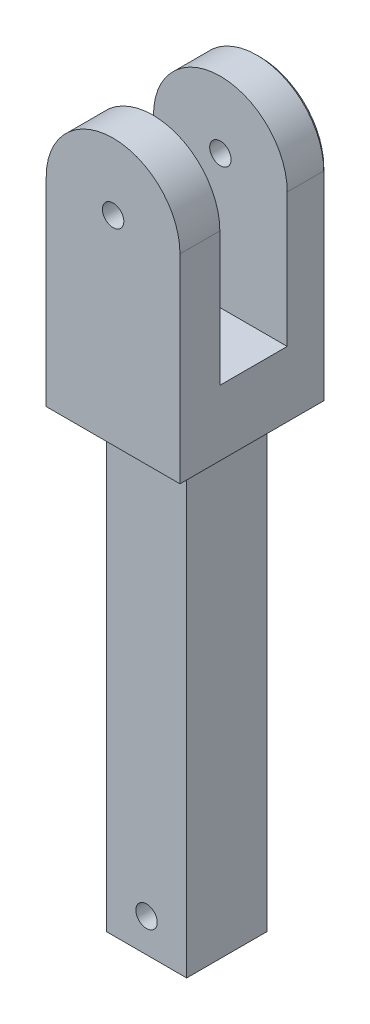
SolidWorks part; units mm, degrees
ref_plane "前基準面" through (0, 0, 0) normal (0, 0, 1) x (1, 0, 0)
ref_plane "上基準面" through (0, 0, 0) normal (0, 1, 0) x (1, 0, 0)
ref_plane "右基準面" through (0, 0, 0) normal (1, 0, 0) x (0, 0, -1)
sketch "草圖1" plane through (0, 0, 0) normal (0, 0, 1) x (1, 0, 0)
  line L0 (0, 0) -> (0, -11.05)
  line L1 (-10, 0) -> (-10, -30.2764)
  line L3 (10, -30.2764) -> (10, 0)
  line L4 (-10, -30.2764) -> (10, -30.2764)
  circle A1 centre (0, 0) radius 1.6
  arc A2 (10, 0) -> (-10, 0) centre (0, 0) ccw
  dimension "D1" = 11.05
  dimension "D2" = 3.2
  dimension "D3" = 20
extrude "填料-伸長1" add sketch "草圖1" along normal blind 12 contours L3 A2 L1 A1 region at (0, -11.2647, 0)
sketch "草圖2" plane through (10, 0, 0) normal (1, 0, 0) x (0, 0, -1)
  line L0 (-12, 0) -> (-9.1, 0)
  line L1 (-12, 0) -> (0, 0) construction
  line L2 (-12, 10) -> (-12, 0) construction
  line L3 (0, 0) -> (-2.9, 0)
  line L4 (-6, 0) -> (-3, 0)
  line L5 (-6, 0) -> (-9, 0)
  line L6 (-9, 0) -> (-9, 15.7808)
  line L7 (-9, 15.7808) -> (-3, 15.7808)
  line L8 (-3, 15.7808) -> (-3, 0)
  line L9 (-3, 0) -> (-3, -20)
  line L10 (-9, 0) -> (-8.6005, -20)
  line L11 (-8.6005, -20) -> (-3, -20)
  line M8 (0, 0) -> (-12, 0)
  dimension "D1" = 2.9
  dimension "D2" = 2.9
  dimension "D3" = 3
  dimension "D4" = 3
  dimension "D5" = 20
extrude "除料-伸長1" cut sketch "草圖2" against normal through all contours L8 L7 L6 M8 | L10 L11 L9 M8 region at (10, 7.8904, 6) region at (10, -9.8852, 5.9013)
sketch "草圖11" plane through (10, 0, 0) normal (1, 0, 0) x (0, 0, -1)
  line L0 (-9, 0) -> (-9, -20)
  line L1 (-9, -20) -> (-8.6005, -20)
  line L2 (-9, 0) -> (-8.6005, -20)
extrude "除料-伸長6" cut sketch "草圖11" against normal through all
sketch "草圖12" plane through (0, 0, 12) normal (0, 0, 1) x (1, 0, 0)
  line L0 (-10, 0) -> (-10, -30.2764)
  line L1 (-10, -30.2764) -> (10, -30.2764)
  line L2 (10, -30.2764) -> (10, 0)
  circle A0 centre (0, 0) radius 1.45
  circle A1 centre (0, 0) radius 10
  circle M1 centre (0, 0) radius 1.6
  line M2 (10, -30.2764) -> (10, 0)
  arc M3 (10, 0) -> (-10, 0) centre (0, 0) ccw
  line M4 (-10, 0) -> (-10, -30.2764)
  line M5 (-10, -30.2764) -> (10, -30.2764)
extrude "填料-伸長11" add sketch "草圖12" along normal blind 5 contours A1 M3 M1 | A1 M4 M5 M2 region at (0, -18.9541, 12) region at (0, 9.7172, 12)
sketch "草圖13" plane through (0, 0, 0) normal (0, 0, -1) x (-1, 0, 0)
  line L0 (-10, 0) -> (-10, -30.2764)
  line L1 (-10, -30.2764) -> (10, -30.2764)
  line L2 (10, 0) -> (10, -30.2764) construction
  line L3 (10, -30.2764) -> (-10, -30.2764) construction
  line L4 (10, -30.2764) -> (10, 0)
  circle A0 centre (0, 0) radius 1.45
  circle A1 centre (0, 0) radius 10
  circle M1 centre (0, 0) radius 1.6
  line M2 (-10, 0) -> (-10, -30.2764)
  line M3 (-10, -30.2764) -> (10, -30.2764)
  line M4 (10, -30.2764) -> (10, 0)
  arc M5 (10, 0) -> (-10, 0) centre (0, 0) ccw
extrude "填料-伸長12" add sketch "草圖13" along normal blind 5 contours A1 M5 M1 | A1 M2 M3 M4 region at (0, -18.9541, 0) region at (0, 9.7172, 0)
sketch "草圖14" plane through (-10, 0, 0) normal (-1, 0, 0) x (0, 0, 1)
  line L0 (3, -20) -> (0.96, -20)
  line L1 (0.96, -20) -> (0.96, 10)
  line L2 (3, 10) -> (-5, 10) construction
  line L3 (0.96, 10) -> (3, 10)
  line L5 (3, 10) -> (11.04, 10)
  line L6 (9, -20) -> (11.04, -20)
  line L7 (11.04, -20) -> (11.04, 10)
  line L8 (17, 10) -> (9, 10) construction
  line L9 (0.96, 10) -> (11.04, 10)
  line L10 (11.04, -20) -> (0.96, -20)
  line L11 (0.96, 10) -> (0.96, -20)
  line L12 (0.96, 10) -> (11.04, 10)
  line M7 (9, 0) -> (9, -20)
  line M8 (9, -20) -> (3, -20)
  line M9 (3, -20) -> (3, 0)
  line M10 (3, 0) -> (-5, 0)
  line M14 (17, 0) -> (9, 0)
  dimension "D1" = 2.04
  dimension "D2" = 2.04
extrude "除料-伸長7" cut sketch "草圖14" against normal through all contours L7 L5 L3 L1 M14 M10 M9 M8 M7 | L1 L0 M9 M10 | L6 L7 M14 M7 region at (-10, -3.1522, 6) region at (-10, -10, 1.98) region at (-10, -10, 10.02)
sketch "草圖15" plane through (0, -30.2764, 0) normal (0, -1, 0) x (1, 0, 0)
  line L0 (-10, 6) -> (10, 6)
  line L1 (-10, 17) -> (-10, -5) construction
  line L2 (10, 17) -> (10, -5) construction
  line L3 (0, 17) -> (0, -5)
  line L4 (-10, 17) -> (10, 17) construction
  line L5 (10, -5) -> (-10, -5) construction
  line L7 (-6, 0) -> (6, 0)
  line L8 (-6, 0) -> (-6, 12)
  line L9 (-6, 12) -> (6, 12)
  line L10 (6, 0) -> (6, 12)
  line L11 (-6, 0) -> (6, 12) construction
  line L12 (-6, 12) -> (6, 0) construction
  point P12 (0, 6)
  dimension "D1" = 12
  dimension "D2" = 12
extrude "填料-伸長13" add sketch "草圖15" along normal blind 68 contours L0 L10 L9 L3 | L9 L8 L0 L3 | L7 L10 L0 L3 | L8 L7 L3 L0 region at (-3, -30.2764, 9) region at (-3, -30.2764, 3) region at (3, -30.2764, 9) region at (3, -30.2764, 3)
sketch "草圖17" plane through (0, 0, 0) normal (0, 0, -1) x (-1, 0, 0)
  line L0 (0, -98.2764) -> (0, -93.2764)
  line L1 (6, -98.2764) -> (-6, -98.2764) construction
  circle A0 centre (0, -93.2764) radius 1.6
  dimension "D2" = 3.2
  dimension "D1" = 5
extrude "除料-伸長8" cut sketch "草圖17" against normal through all contours A0 region at (-1.0994, -94.3758, 0)
chamfer "導角1" distance 0.5 angle 45 7 edges at (-10, -15.1382, -5) (0, -30.2764, -5) (0, 10, -5) (10, -15.1382, -5) (-10, -30.2764, 6) (0, -30.2764, 17) (10, -30.2764, 6)
